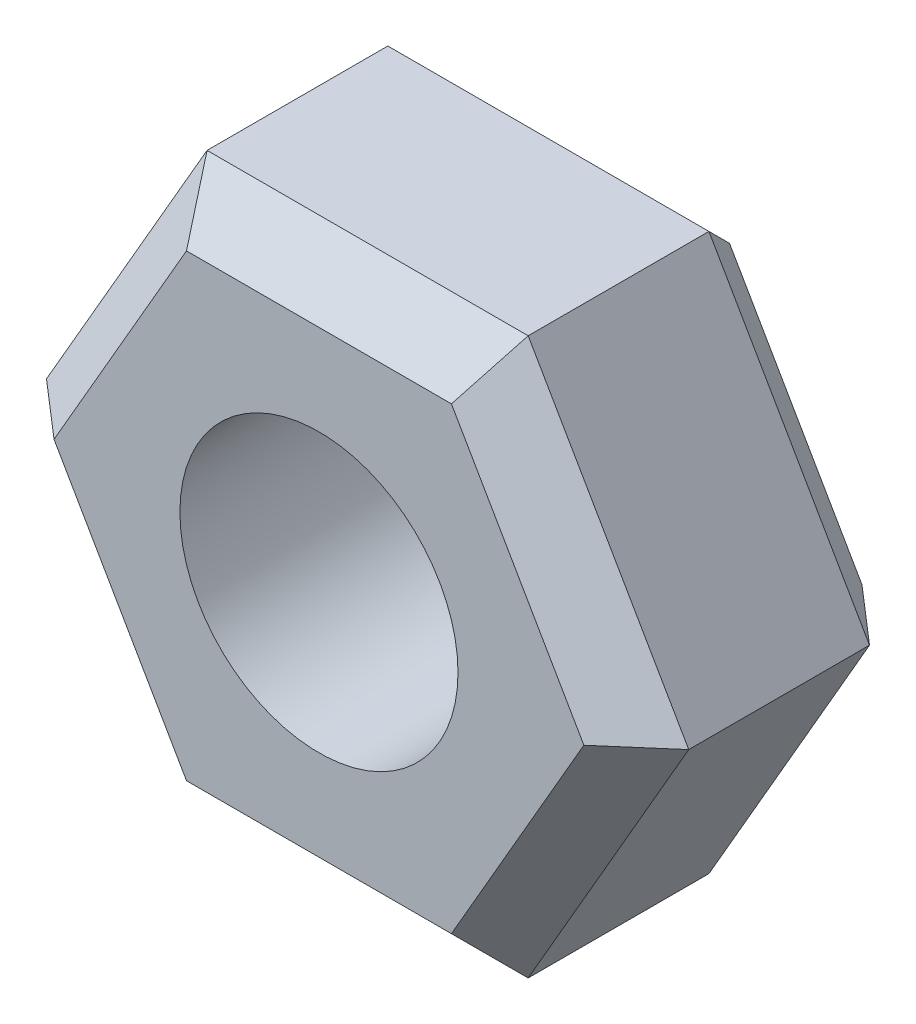
SolidWorks part; units mm, degrees
ref_plane "Front Plane" through (0, 0, 0) normal (0, 0, 1) x (1, 0, 0)
ref_plane "Top Plane" through (0, 0, 0) normal (0, 1, 0) x (1, 0, 0)
ref_plane "Right Plane" through (0, 0, 0) normal (1, 0, 0) x (0, 0, -1)
sketch "Sketch1" plane through (0, 0, 0) normal (0, 0, 1) x (1, 0, 0)
  line L1 (-1.1547, -2) -> (1.1547, -2)
  line L2 (1.1547, -2) -> (2.3094, 0)
  line L3 (2.3094, 0) -> (1.1547, 2)
  line L4 (1.1547, 2) -> (-1.1547, 2)
  line L5 (-1.1547, 2) -> (-2.3094, 0)
  line L6 (-2.3094, 0) -> (-1.1547, -2)
  circle A0 centre (0, 0) radius 2 construction
  circle A1 centre (0, 0) radius 1
  dimension "D2" = 2
  dimension "D1" = 4
extrude "Shape" add sketch "Sketch1" along normal blind 2
chamfer "Chamfer" distance 0.35 angle 45 12 edges at (1.7321, -1, 0) (0, -2, 0) (-1.7321, -1, 0) (-1.7321, 1, 0) (0, 2, 0) (1.7321, 1, 0) (1.7321, 1, 2) (1.7321, -1, 2) (0, -2, 2) (-1.7321, -1, 2) (-1.7321, 1, 2) (0, 2, 2)
ref_axis "Center Axis" through (0, 0, 2) along (0, 0, -1)
